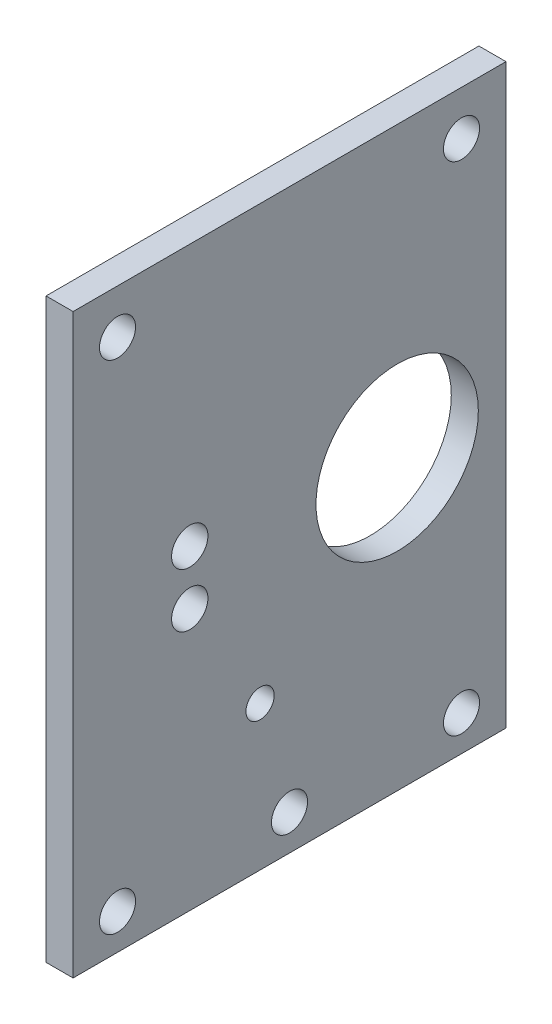
SolidWorks part; units mm, degrees
material "6061 Alloy"
ref_plane "Front Plane" through (0, 0, 0) normal (0, 0, 1) x (1, 0, 0)
ref_plane "Top Plane" through (0, 0, 0) normal (0, 1, 0) x (1, 0, 0)
ref_plane "Right Plane" through (0, 0, 0) normal (1, 0, 0) x (0, 0, -1)
sketch "Sketch2" plane through (0, 0, 0) normal (1, 0, 0) x (0, 0, -1)
  line L1 (-38.1, -50.8) -> (38.1, -50.8)
  line L2 (-38.1, -50.8) -> (-38.1, 50.8)
  line L3 (-38.1, 50.8) -> (38.1, 50.8)
  line L4 (38.1, -50.8) -> (38.1, 50.8)
  line L5 (-38.1, -50.8) -> (38.1, 50.8) construction
  line L6 (-38.1, 50.8) -> (38.1, -50.8) construction
  point P0 (0, 0)
  dimension "D1" = 76.2
  dimension "D2" = 101.6
extrude "Boss-Extrude1" add sketch "Sketch2" along normal blind 4.7625
sketch "Sketch3" plane through (4.7625, 0, 0) normal (1, 0, 0) x (0, 0, -1)
  line L5 (30.2768, -44.5643) -> (-30.2768, -44.5643) construction
  line L6 (-30.2768, 42.9768) -> (30.2768, 42.9768) construction
  line L7 (30.2768, 42.9768) -> (30.2768, -44.5643) construction
  line L8 (-30.2768, 42.9768) -> (-30.2768, -44.5643) construction
  line L9 (-38.1, 50.8) -> (-38.1, -50.8) construction
  line L10 (38.1, 50.8) -> (-38.1, 50.8) construction
  line L11 (38.1, -50.8) -> (38.1, 50.8) construction
  line L12 (-38.1, -50.8) -> (38.1, -50.8) construction
  circle A0 centre (30.2768, -44.5643) radius 3.175
  circle A1 centre (30.2768, 42.9768) radius 3.175
  circle A2 centre (-30.2768, 42.9768) radius 3.175
  circle A3 centre (-30.2768, -44.5643) radius 3.175
  circle A4 centre (18.9484, 0) radius 14.2875
  circle A5 centre (-5.1816, -25.4) radius 2.4892
  circle A6 centre (0, -44.5643) radius 3.175
  dimension "D1" = 6.35
  dimension "D5" = 7.8232
  dimension "D7" = 7.8232
  dimension "D8" = 6.2357
  dimension "D9" = 28.575
  dimension "D10" = 50.8
  dimension "D11" = 4.9784
  dimension "D12" = 25.4
  dimension "D6" = 7.8232
  dimension "D13" = 24.13
  dimension "D14" = 19.1516
extrude "Cut-Extrude1" cut sketch "Sketch3" against normal blind 6.35 contours A1
extrude "Cut-Extrude2" cut sketch "Sketch3<4>" against normal blind 6.35
sketch "Sketch3<4>" plane through (4.7625, 0, 0) normal (1, 0, 0) x (0, 0, -1) same geometry as "Sketch3"
hole_wizard "M6 Clearance Hole1" positions "Sketch5" profile "Sketch4" hole size "M6" standard "ANSI Metric" end condition up to next
sketch "Sketch5" plane through (4.7625, 0, 0) normal (1, 0, 0) x (0, 0, -1)
  circle A0 centre (-17.5641, -4.7625) radius 1.65 construction
  circle A1 centre (-17.5641, 4.7625) radius 1.65 construction
  point P0 (-17.5641, 4.7625)
  point P2 (-17.5641, -4.7625)
sketch "Sketch4" plane through (4.7625, 4.7625, 17.5641) normal (0, 1, 0) x (0, 0, -1)
  line L0 (0, 0) -> (0, 4.7625)
  line L1 (0, 4.7625) -> (3.2, 4.7625)
  line L2 (3.2, 4.7625) -> (3.2, 0)
  line L5 (3.2, 0) -> (0, 0)
  line L11 (0, -6.35) -> (0, 107.95) construction
  dimension "Thru Hole Dia." = 6.4
  dimension "Thru Hole Depth" = 4.7625
